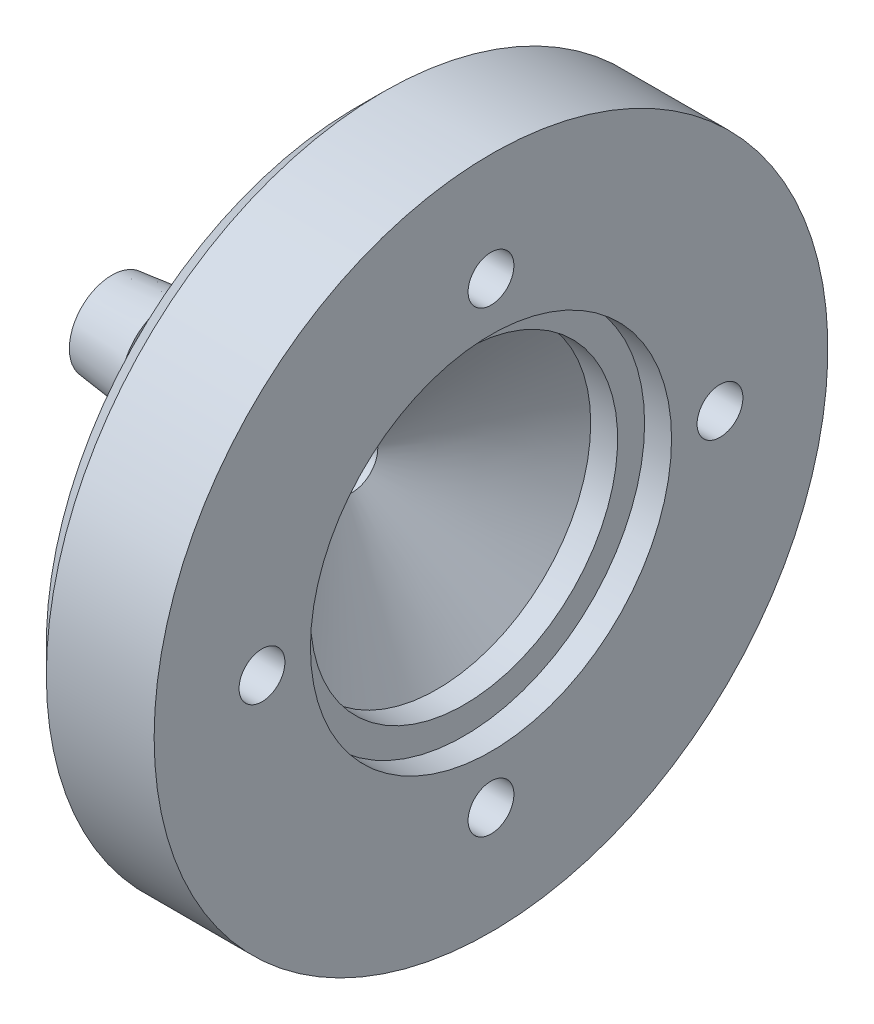
SolidWorks part; units mm, degrees
ref_plane "Front Plane" through (0, 0, 0) normal (0, 0, 1) x (1, 0, 0)
ref_plane "Top Plane" through (0, 0, 0) normal (0, 1, 0) x (1, 0, 0)
ref_plane "Right Plane" through (0, 0, 0) normal (1, 0, 0) x (0, 0, -1)
sketch "Sketch1" plane through (0, 0, 0) normal (0, 0, 1) x (1, 0, 0)
  line L0 (-801.9206, 0) -> (36107.5283, 0) construction
  line L3 (-13.5058, 3.65) -> (-13.5058, 3.15)
  line L8 (-17.8392, 1.9) -> (0, 1.9)
  line L9 (-17.8392, 1.9) -> (-17.8392, 3.15)
  line L10 (10.3016, 13.4) -> (10.3016, 25)
  line L12 (10.3016, 25) -> (0.3016, 25)
  line L16 (10.3016, 13.4) -> (8.3016, 13.4)
  line L17 (8.3016, 13.4) -> (8.3016, 11.4)
  line L18 (0.3016, 25) -> (0.3016, 11.4)
  line L20 (0, 1.9) -> (6.3016, 11.4)
  line L21 (-17.8392, 3.15) -> (-13.5058, 3.65)
  line L22 (6.3016, 11.4) -> (8.3016, 11.4)
  line L23 (-13.5058, 3.15) -> (-9.1725, 3.65)
  line L25 (-9.1725, 3.15) -> (-4.8392, 3.65)
  line L26 (-9.1725, 3.65) -> (-9.1725, 3.15)
  line L27 (-4.8392, 3.65) -> (0.3016, 11.4)
  dimension "D3" = 2
  dimension "D2" = 7.3
  dimension "D6" = 3.8
  dimension "D7" = 6.3
  dimension "D1" = 10
  dimension "D5" = 25
  dimension "D8" = 13.4
  dimension "D10" = 2
  dimension "D4" = 5
  dimension "D9" = 2
  dimension "D11" = 13
revolve "Revolve17" add sketch "Sketch1" angle 360 about L0
sketch "Sketch4" plane through (0.3016, 0, 0) normal (-1, 0, 0) x (0, 0, 1)
  circle A0 centre (0, 0) radius 16.9947 construction
  point P3 (0, 16.9947)
  point P7 (16.9947, 0)
  point P12 (-16.9947, 0)
  point P13 (0, -16.9947)
hole_wizard "CBORE for M3 Hex Socket Head Cap Screw2" positions "Sketch4" profile "Sketch5" counterbore size "M3" standard "ISO"
sketch "Sketch5" plane through (0.3016, -16.9947, 0) normal (0, 1, 0) x (0, 0, 1)
  line L0 (0, 0) -> (0, 11.0215)
  line L1 (0, 11.0215) -> (1.7, 10)
  line L2 (1.7, 10) -> (1.7, 3.4)
  line L3 (1.7, 3.4) -> (3.25, 3.4)
  line L4 (3.25, 3.4) -> (3.25, 0)
  line L5 (3.25, 0) -> (0, 0)
  line L10 (0, 11.0215) -> (-1.7, 10) construction
  line L11 (0, -6.35) -> (0, 107.95) construction
  dimension "Hole Dia." = 3.4
  dimension "Hole Depth" = 10
  dimension "C'Bore Dia." = 6.5
  dimension "C'Bore Depth" = 3.4
  dimension "Drill Angle" = 118
chamfer "Chamfer1" distance 2 angle 45 1 edges at (0.3016, 0, 25)
equation "\"D10@Sketch1\"=\"D3@Sketch1\""
equation "\"D9@Sketch1\"=\"D3@Sketch1\""
